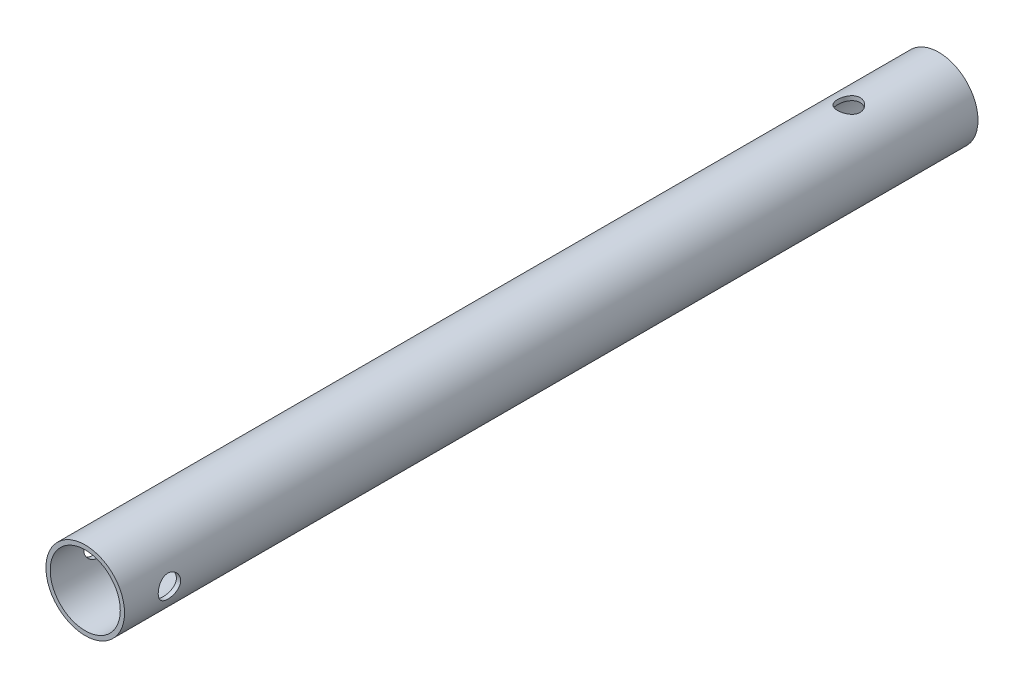
SolidWorks part; units mm, degrees
ref_plane "Front Plane" through (0, 0, 0) normal (0, 0, 1) x (1, 0, 0)
ref_plane "Top Plane" through (0, 0, 0) normal (0, 1, 0) x (1, 0, 0)
ref_plane "Right Plane" through (0, 0, 0) normal (1, 0, 0) x (0, 0, -1)
sketch "Sketch1" plane through (0, 0, 0) normal (0, 0, 1) x (1, 0, 0)
  circle A0 centre (0, 0) radius 22.225 construction
  circle A1 centre (0, 0) radius 19.812 construction
  point P3 (-22.225, 0)
  point P4 (22.225, 0)
  point P6 (-19.812, 0)
  point P7 (19.812, 0)
  dimension "OD" = 44.45
  dimension "Wall" = 2.413
  dimension "ID" = 39.624
sketch "Sketch2" plane through (0, 0, 0) normal (1, 0, 0) x (0, 0, -1)
  line L0 (241.3, 0) -> (-241.3, 0) construction
  line L2 (0, 22.225) -> (0, -22.225) construction
  line L3 (0, 22.225) -> (0, -22.225) construction
  line L4 (241.3, 22.225) -> (-241.3, 22.225) construction
  line L5 (241.3, -22.225) -> (-241.3, -22.225) construction
  line L6 (-241.3, -22.225) -> (-241.3, 22.225) construction
  line L7 (241.3, -22.225) -> (241.3, 22.225) construction
  line L8 (-196.85, -22.225) -> (-196.85, 22.225) construction
  line L9 (196.85, -22.225) -> (196.85, 22.225) construction
  point P3 (0, 0)
  point P9 (0, 22.225)
  point P11 (0, -22.225)
  point P13 (-241.3, 0)
  point P14 (241.3, 22.225)
  point P15 (-241.3, -22.225)
  point P16 (-241.3, 22.225)
  point P17 (-241.3, 0)
  point P18 (241.3, -22.225)
  point P19 (241.3, 0)
  point P22 (-196.85, 0)
  point P25 (196.85, 0)
  point P26 (-196.85, -22.225)
  point P27 (-196.85, 22.225)
  point P28 (196.85, 22.225)
  point P29 (196.85, -22.225)
  dimension "Length" = 482.6
  dimension "D1" = 44.45
sketch "Sketch3" plane through (0, 0, 0) normal (0, 0, 1) x (1, 0, 0)
  circle A0 centre (0, 0) radius 22.225 construction
  circle A1 centre (0, 0) radius 19.812 construction
  circle A2 centre (0, 0) radius 22.225
  circle A3 centre (0, 0) radius 19.812
extrude "Boss-Extrude1" add sketch "Sketch3" along normal mid plane 482.6
ref_plane "Plane1" through (0, 22.225, 0) normal (0, 1, 0) x (1, 0, 0)
sketch "Sketch4" plane through (0, 22.225, 0) normal (0, 1, 0) x (1, 0, 0)
  line L0 (19.812, 241.3) -> (-19.812, 241.3) construction
  line L1 (22.225, -241.3) -> (22.225, 241.3) construction
  circle A0 centre (0, 190.5) radius 6.35
  dimension "D1" = 12.7
  dimension "D2" = 50.8
  dimension "D3" = 22.225
extrude "Cut-Extrude1" cut sketch "Sketch4" against normal through all
ref_plane "Plane2" through (22.225, 0, 0) normal (1, 0, 0) x (0, 0, -1)
sketch "Sketch5" plane through (22.225, 0, 0) normal (1, 0, 0) x (0, 0, -1)
  line L0 (184.15, 22.225) -> (-241.3, 22.225) construction
  line L1 (-241.3, 22.225) -> (-241.3, -22.225) construction
  circle A0 centre (-215.9, 0) radius 6.35
  dimension "D1" = 12.7
  dimension "D2" = 22.225
  dimension "D3" = 25.4
extrude "Cut-Extrude2" cut sketch "Sketch5" against normal through all
equation "\"D1@Sketch2\"=\"OD@Sketch1\""
equation "\"D1@Boss-Extrude1\"=\"Length@Sketch2\""
